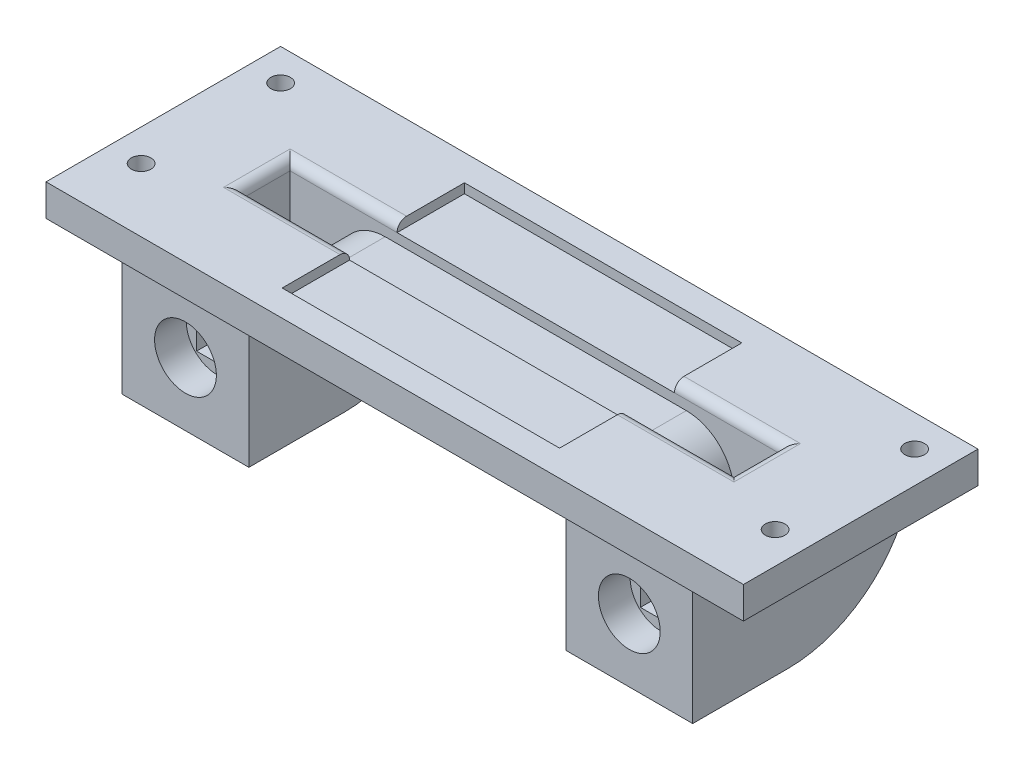
SolidWorks part; units mm, degrees
ref_plane "Front Plane" through (0, 0, 0) normal (0, 0, 1) x (1, 0, 0)
ref_plane "Top Plane" through (0, 0, 0) normal (0, 1, 0) x (1, 0, 0)
ref_plane "Right Plane" through (0, 0, 0) normal (1, 0, 0) x (0, 0, -1)
sketch "Sketch1" plane through (0, 0, 0) normal (0, 1, 0) x (1, 0, 0)
  line L0 (-999.8545, 13.5) -> (49000.1455, 13.5) construction
  line L1 (55, -18.5) -> (-55, -18.5)
  line L2 (55, -18.5) -> (55, 18.5)
  line L3 (55, 18.5) -> (-55, 18.5)
  line L4 (-55, -18.5) -> (-55, 18.5)
  line L5 (55, -18.5) -> (-55, 18.5) construction
  line L6 (55, 18.5) -> (-55, -18.5) construction
  line L7 (-1001.6005, -8.5) -> (48998.3995, -8.5) construction
  line L8 (-50, -1003.955) -> (-50, 48996.045) construction
  line L9 (50, -1000.463) -> (50, 48999.537) construction
  circle A0 centre (50, -8.5) radius 1.55
  circle A1 centre (50, 13.5) radius 1.55
  circle A2 centre (-50, 13.5) radius 1.55
  circle A3 centre (-50, -8.5) radius 1.55
  point P0 (0, 0)
  dimension "D8" = 3.1
  dimension "D10" = 3.1
  dimension "D12" = 3.1
  dimension "D14" = 3.1
  dimension "D1" = 110
  dimension "D2" = 37
  dimension "D3" = 5
  dimension "D4" = 5
  dimension "D5" = 10
  dimension "D6" = 5
  dimension "D7" = 0
  dimension "D9" = 0
  dimension "D11" = 0
  dimension "D13" = 0
extrude "Boss-Extrude1" add sketch "Sketch1" along normal blind 5
sketch "Sketch2" plane through (0, 5, 0) normal (0, 1, 0) x (1, 0, 0)
  line L1 (-21.875, -14.375) -> (21.875, -14.375)
  line L2 (-21.875, -14.375) -> (-21.875, 14.375)
  line L3 (-21.875, 14.375) -> (21.875, 14.375)
  line L4 (21.875, -14.375) -> (21.875, 14.375)
  line L5 (-21.875, -14.375) -> (21.875, 14.375) construction
  line L6 (-21.875, 14.375) -> (21.875, -14.375) construction
  point P0 (0, 0)
  dimension "D1" = 43.75
  dimension "D2" = 28.75
extrude "Cut-Extrude1" cut sketch "Sketch2" against normal blind 1.5
sketch "Sketch3" plane through (0, 0, 0) normal (0, -1, 0) x (-1, 0, 0)
  line L0 (35, -1001.3549) -> (35, 48998.6451) construction
  line L1 (-35, -998.3063) -> (-35, 49001.6937) construction
  line L2 (-1000, 0) -> (49000, 0) construction
  line L3 (55, 18.5) -> (55, -18.5) construction
  line L4 (-55, -18.5) -> (-55, 18.5) construction
  line L5 (-55, 18.5) -> (55, 18.5) construction
  line L6 (25, 18.5) -> (45, 18.5)
  line L7 (25, 18.5) -> (25, -16.5)
  line L8 (25, -16.5) -> (45, -16.5)
  line L9 (45, 18.5) -> (45, -16.5)
  line L10 (25, 18.5) -> (45, -16.5) construction
  line L11 (25, -16.5) -> (45, 18.5) construction
  line L12 (-45, 18.5) -> (-25, 18.5)
  line L13 (-45, 18.5) -> (-45, -16.5)
  line L14 (-45, -16.5) -> (-25, -16.5)
  line L15 (-25, 18.5) -> (-25, -16.5)
  line L16 (-45, 18.5) -> (-25, -16.5) construction
  line L17 (-45, -16.5) -> (-25, 18.5) construction
  point P11 (35, 1)
  point P16 (-35, 1)
  dimension "D1" = 20
  dimension "D2" = 20
  dimension "D3" = 20
  dimension "D4" = 20
  dimension "D5" = 0
  dimension "D6" = 0
  dimension "D7" = 35
  dimension "D8" = 35
extrude "Boss-Extrude2" add sketch "Sketch3" along normal blind 20
fillet "Fillet1" radius 20 2 edges at (35, -20, -18.5) (-35, -20, -18.5)
sketch "Sketch4" plane through (0, 5, 0) normal (0, 1, 0) x (1, 0, 0)
  line L0 (-35, -999.8871) -> (-35, 49000.1129) construction
  line L1 (35, -999.4354) -> (35, 49000.5646) construction
  line L2 (-1000, 0) -> (49000, 0) construction
  line L3 (-55, 18.5) -> (-55, -18.5) construction
  line L4 (55, -18.5) -> (55, 18.5) construction
  line L6 (-31.25, -3.75) -> (-38.75, -3.75)
  line L7 (-31.25, -3.75) -> (-31.25, 3.75)
  line L8 (-31.25, 3.75) -> (-38.75, 3.75)
  line L9 (-38.75, -3.75) -> (-38.75, 3.75)
  line L10 (-31.25, -3.75) -> (-38.75, 3.75) construction
  line L11 (-31.25, 3.75) -> (-38.75, -3.75) construction
  line L12 (38.75, -3.75) -> (31.25, -3.75)
  line L13 (38.75, -3.75) -> (38.75, 3.75)
  line L14 (38.75, 3.75) -> (31.25, 3.75)
  line L15 (31.25, -3.75) -> (31.25, 3.75)
  line L16 (38.75, -3.75) -> (31.25, 3.75) construction
  line L17 (38.75, 3.75) -> (31.25, -3.75) construction
  point P11 (-35, 0)
  point P16 (35, 0)
  dimension "D1" = 20
  dimension "D2" = 20
  dimension "D3" = 7.5
  dimension "D4" = 7.5
  dimension "D5" = 7.5
  dimension "D6" = 7.5
extrude "Cut-Extrude2" cut sketch "Sketch4" against normal blind 18.75
sketch "Sketch5" plane through (0, 0, 16.5) normal (0, 0, 1) x (1, 0, 0)
  line L0 (-1033.8733, -10) -> (48966.1267, -10) construction
  line L1 (-35, -1020) -> (-35, 48980) construction
  line L2 (-25, -20) -> (-45, -20) construction
  line L3 (35, -1020) -> (35, 48980) construction
  line L4 (45, -20) -> (25, -20) construction
  line L6 (-38.25, -13.25) -> (-31.75, -13.25)
  line L7 (-38.25, -13.25) -> (-38.25, -6.75)
  line L8 (-38.25, -6.75) -> (-31.75, -6.75)
  line L9 (-31.75, -13.25) -> (-31.75, -6.75)
  line L10 (-38.25, -13.25) -> (-31.75, -6.75) construction
  line L11 (-38.25, -6.75) -> (-31.75, -13.25) construction
  line L12 (31.75, -13.25) -> (38.25, -13.25)
  line L13 (31.75, -13.25) -> (31.75, -6.75)
  line L14 (31.75, -6.75) -> (38.25, -6.75)
  line L15 (38.25, -13.25) -> (38.25, -6.75)
  line L16 (31.75, -13.25) -> (38.25, -6.75) construction
  line L17 (31.75, -6.75) -> (38.25, -13.25) construction
  point P7 (-35, -20)
  point P8 (-35, -10)
  point P12 (35, -20)
  point P17 (35, -10)
  dimension "D1" = 10
  dimension "D2" = 6.5
  dimension "D3" = 6.5
  dimension "D4" = 6.5
  dimension "D5" = 6.5
extrude "Cut-Extrude3" cut sketch "Sketch5" against normal blind 15
fillet "Fillet2" radius 7.5 4 edges at (35, -6.75, 3.75) (35, -13.75, -3.75) (-35, -13.75, -3.75) (-35, -6.75, 3.75)
chamfer "Chamfer1" distance 0.5 angle 45 6 edges at (-31.75, -6.25, 3.75) (-35, -13.25, 3.75) (-38.25, -6.25, 3.75) (38.25, -6.25, 3.75) (35, -13.25, 3.75) (31.75, -6.25, 3.75)
sketch "Sketch7" plane through (0, 0, 16.5) normal (0, 0, 1) x (1, 0, 0)
  line L0 (-35, -1013.25) -> (-35, 48986.75) construction
  line L1 (-38.25, -13.25) -> (-31.75, -13.25) construction
  line L2 (35, -1013.25) -> (35, 48986.75) construction
  line L3 (31.75, -13.25) -> (38.25, -13.25) construction
  line L4 (-1031.75, -10) -> (48968.25, -10) construction
  line L5 (-31.75, -13.25) -> (-31.75, -6.75) construction
  circle A0 centre (-35, -10) radius 4.875
  circle A1 centre (35, -10) radius 4.875
  point P5 (-35, -13.25)
  point P10 (35, -13.25)
  point P15 (-31.75, -10)
  dimension "D2" = 9.75
  dimension "D4" = 9.75
  dimension "D1" = 0
  dimension "D3" = 0
extrude "Cut-Extrude5" cut sketch "Sketch7" against normal blind 5
sketch "Sketch8" plane through (0, 0, 0) normal (0, -1, 0) x (1, 0, 0)
  circle A0 centre (-50, 8.5) radius 2.75
  circle A1 centre (-50, -13.5) radius 2.75
  circle A2 centre (50, -13.5) radius 2.75
  circle A3 centre (50, 8.5) radius 2.75
  dimension "D1" = 5.5
  dimension "D2" = 5.5
  dimension "D3" = 5.5
  dimension "D4" = 5.5
extrude "Cut-Extrude6" cut sketch "Sketch8" against normal blind 2
sketch "Sketch9" plane through (0, 5, 0) normal (0, 1, 0) x (1, 0, 0)
  line L1 (-31.25, 3.75) -> (31.25, 3.75)
  line L2 (-31.25, 3.75) -> (-31.25, -3.75)
  line L3 (-31.25, -3.75) -> (31.25, -3.75)
  line L4 (31.25, 3.75) -> (31.25, -3.75)
extrude "Cut-Extrude7" cut sketch "Sketch9" against normal blind 3
fillet "Fillet3" radius 7.5 2 edges at (-31.25, 2, 0) (31.25, 2, 0)
fillet "Fillet4" radius 1.5 6 edges at (-38.75, 5, 0) (-30.3125, 5, -3.75) (-30.3125, 5, 3.75) (38.75, 5, 0) (30.3125, 5, 3.75) (30.3125, 5, -3.75)
